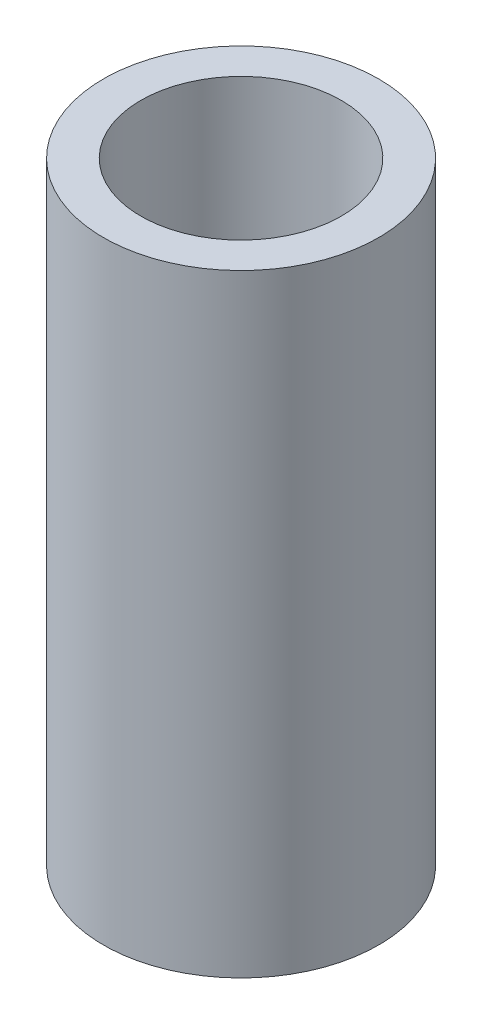
SolidWorks part; units mm, degrees
ref_plane "Front Plane" through (0, 0, 0) normal (0, 0, 1) x (1, 0, 0)
ref_plane "Top Plane" through (0, 0, 0) normal (0, 1, 0) x (1, 0, 0)
ref_plane "Right Plane" through (0, 0, 0) normal (1, 0, 0) x (0, 0, -1)
sketch "Sketch1" plane through (0, 0, 0) normal (0, 1, 0) x (1, 0, 0)
  circle A0 centre (0, 0) radius 25
  dimension "SLEEVE_OD" = 50
extrude "Boss-Extrude1" add sketch "Sketch1" along normal blind 111.3525
sketch "Sketch2" plane through (0, 0, 0) normal (0, 1, 0) x (1, 0, 0)
  circle A0 centre (0, 0) radius 18.2283
  dimension "BORE_D" = 36.4565
extrude "Cut-Extrude1" cut sketch "Sketch2" along normal through all
chamfer "Chamfer1" distance 3.5585 angle 60 rebuild error yes
